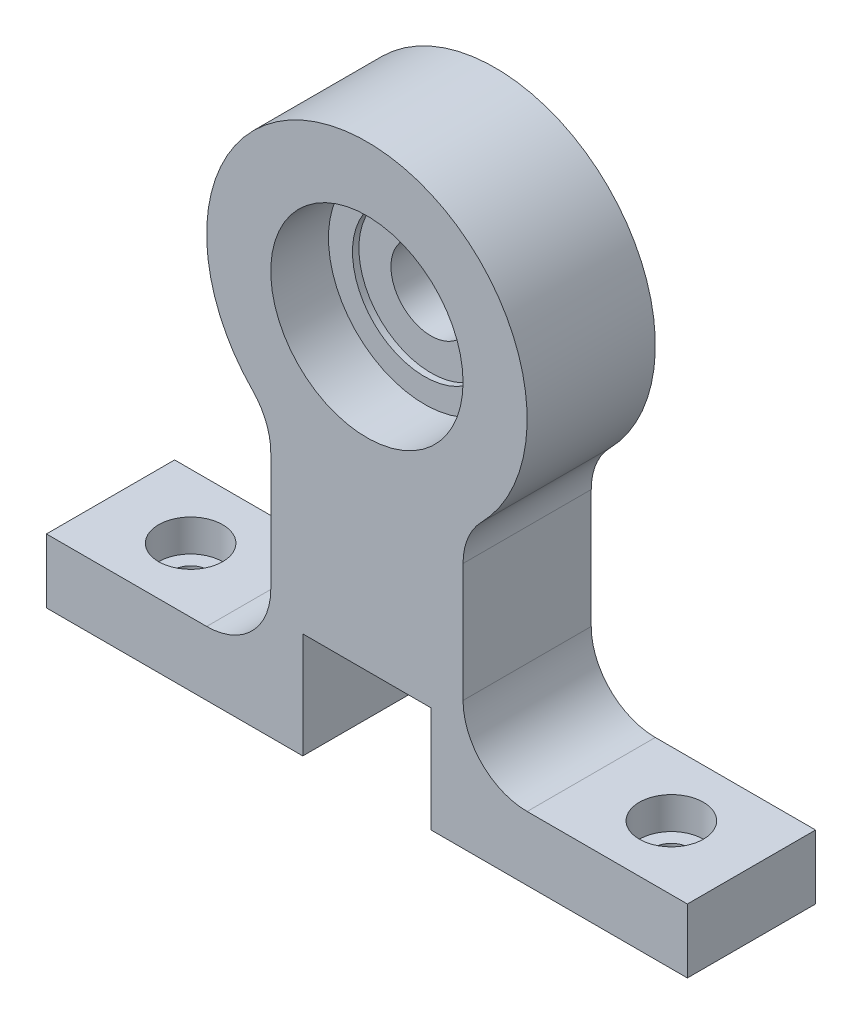
SolidWorks part; units mm, degrees
ref_plane "Front Plane" through (0, 0, 0) normal (0, 0, 1) x (1, 0, 0)
ref_plane "Top Plane" through (0, 0, 0) normal (0, 1, 0) x (1, 0, 0)
ref_plane "Right Plane" through (0, 0, 0) normal (1, 0, 0) x (0, 0, -1)
sketch "Sketch1" plane through (0, 0, 0) normal (0, 0, 1) x (1, 0, 0)
  line L0 (15, 43) -> (15, 10)
  line L1 (-50, 0) -> (50, 0)
  line L2 (-50, 0) -> (-50, 10)
  line L3 (-50, 10) -> (-15, 10)
  line L4 (50, 0) -> (50, 10)
  line L5 (-15, 43) -> (-15, 10)
  line L6 (0, 0) -> (0, 63) construction
  line L7 (15, 10) -> (50, 10)
  circle A0 centre (0, 63) radius 15
  arc A1 (15, 43) -> (-15, 43) centre (0, 63) ccw
  circle A2 centre (0, 63) radius 25 construction
  point P4 (0, 0)
  dimension "D1" = 30
  dimension "D3" = 63
  dimension "D4" = 100
  dimension "D5" = 10
  dimension "D2" = 10
extrude "Boss-Extrude1" add sketch "Sketch1" along normal mid plane 20
sketch "Sketch2" plane through (0, 0, 0) normal (0, 0, 1) x (1, 0, 0)
  circle A0 centre (0, 63) radius 15 construction
  circle A1 centre (0, 63) radius 15
  circle A2 centre (0, 63) radius 6.25
  dimension "D1" = 12.5
extrude "Boss-Extrude2" add sketch "Sketch2" against normal through all
fillet "Fillet1" radius 10 4 edges at (15, 43, 0) (-15, 43, 0) (-15, 10, 0) (15, 10, 0)
hole_wizard "CBORE for M5 SHCS1" positions "Sketch3" profile "Sketch4" counterbore size "M5" standard "ANSI Metric" end condition through all
sketch "Sketch3" plane through (0, 10, 0) normal (0, 1, 0) x (1, 0, 0)
  line L0 (-37.5, 0) -> (37.5, 0)
  point P0 (-37.5, 0)
  point P2 (37.5, 0)
  dimension "D1" = 75
sketch "Sketch4" plane through (-37.5, 10, 0) normal (1, 0, 0) x (0, 0, 1)
  line L0 (0, 0) -> (0, 10)
  line L1 (0, 10) -> (2.75, 10)
  line L3 (2.75, 10) -> (2.75, 5)
  line L4 (2.75, 5) -> (5, 5)
  line L5 (5, 5) -> (5, 0)
  line L7 (5, 0) -> (0, 0)
  line L11 (0, -6.35) -> (0, 107.95) construction
  dimension "Thru Hole Dia." = 5.5
  dimension "Thru Hole Depth" = 10
  dimension "C'Bore Dia." = 10
  dimension "C'Bore Depth" = 5
sketch "Sketch5" plane through (0, 0, 0) normal (0, 0, 1) x (1, 0, 0)
  circle A0 centre (0, 63) radius 11.25
  circle A1 centre (0, 63) radius 15 construction
  circle A2 centre (0, 63) radius 15
  dimension "D1" = 22.5
extrude "Boss-Extrude3" add sketch "Sketch5" along normal blind 1
sketch "Sketch6" plane through (0, 0, 0) normal (0, 0, 1) x (1, 0, 0)
  line L0 (-50, 0) -> (50, 0) construction
  line L1 (-10, 0) -> (10, 0)
  line L2 (-10, 0) -> (-10, 16.5)
  line L3 (-10, 16.5) -> (10, 16.5)
  line L4 (10, 0) -> (10, 16.5)
  point P6 (0, 16.5)
  dimension "D1" = 20
  dimension "D2" = 16.5
extrude "Cut-Extrude1" cut sketch "Sketch6" against normal through all both and the other way through all
